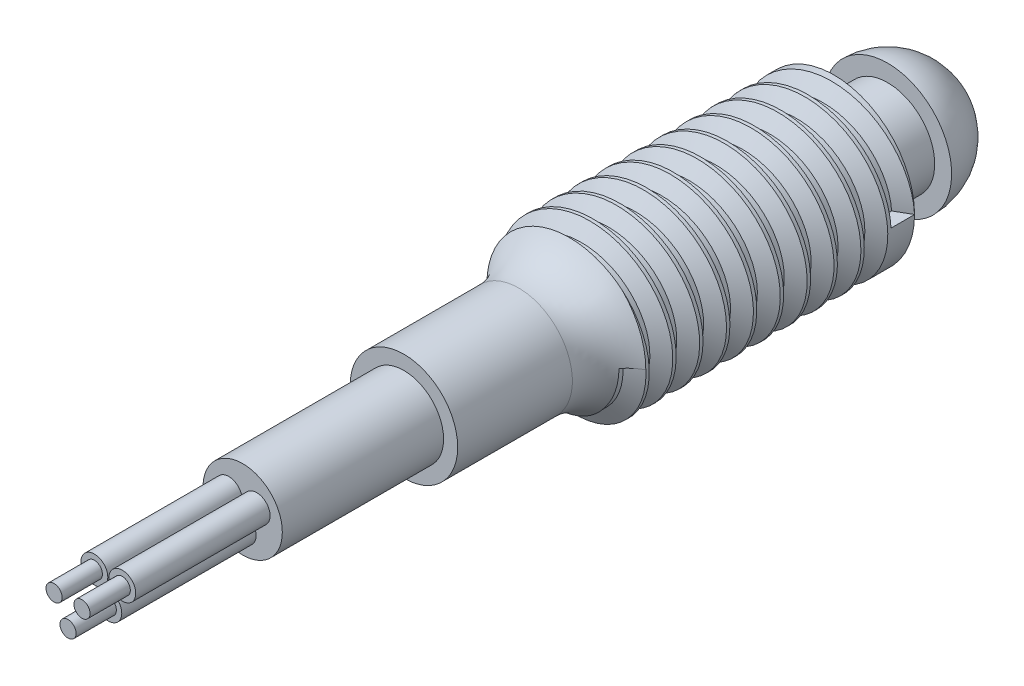
SolidWorks part; units mm, degrees
ref_plane "Front Plane" through (0, 0, 0) normal (0, 0, 1) x (1, 0, 0)
ref_plane "Top Plane" through (0, 0, 0) normal (0, 1, 0) x (1, 0, 0)
ref_plane "Right Plane" through (0, 0, 0) normal (1, 0, 0) x (0, 0, -1)
sketch "Sketch2" plane through (0, 0, 0) normal (0, 0, 1) x (1, 0, 0)
  line L0 (0, 3.833) -> (0, -4.6433) construction
  line L1 (0, 2.38) -> (0, -2.38)
  arc A0 (0, 2.38) -> (0, -2.38) centre (0, 0) ccw
  dimension "D1" = 4.76
revolve "Revolve2" add sketch "Sketch2" angle 180 about L0
sketch "Sketch3" plane through (0, 0, 0) normal (0, 0, 1) x (1, 0, 0)
  circle A0 centre (0, 0) radius 1.75
  dimension "D1" = 3.5
extrude "Boss-Extrude1" add sketch "Sketch3" along normal blind 2
sketch "Sketch4" plane through (0, 0, 2) normal (0, 0, 1) x (1, 0, 0)
  circle A0 centre (0, 0) radius 3
  dimension "D1" = 6
extrude "Boss-Extrude2" add sketch "Sketch4" along normal blind 10
sketch "Sketch5" plane through (0, 0, 12) normal (0, 0, 1) x (1, 0, 0)
  circle A0 centre (0, 0) radius 2
  dimension "D1" = 4
extrude "Boss-Extrude3" add sketch "Sketch5" along normal blind 6
fillet "Fillet1" radius 2 1 edges at (2, 0, 12)
sketch "Sketch6" plane through (0, 0, 18) normal (0, 0, 1) x (1, 0, 0)
  circle A0 centre (0, 0) radius 1.4745
extrude "Boss-Extrude4" add sketch "Sketch6" along normal blind 6
sketch "Sketch7" plane through (0, 0, 24) normal (0, 0, 1) x (1, 0, 0)
  line L0 (0, 0) -> (0, -0.6) construction
  line L1 (0, -0.6) -> (0.5196, 0.3) construction
  line L2 (0.5196, 0.3) -> (-0.5196, 0.3) construction
  line L3 (-0.5196, 0.3) -> (0, -0.6) construction
  circle A0 centre (0, 0) radius 0.3 construction
  circle A1 centre (-0.5196, 0.3) radius 0.5
  circle A2 centre (0.5196, 0.3) radius 0.5
  circle A3 centre (0, -0.6) radius 0.5
  dimension "D1" = 0.6
  dimension "D2" = 1
extrude "Boss-Extrude5" add sketch "Sketch7" along normal blind 5
sketch "Sketch8" plane through (0, 0, 29) normal (0, 0, 1) x (1, 0, 0)
  circle A0 centre (-0.5196, 0.3) radius 0.3
  circle A1 centre (0.5196, 0.3) radius 0.3
  circle A2 centre (0, -0.6) radius 0.3
  dimension "D1" = 0.6
extrude "Boss-Extrude6" add sketch "Sketch8" along normal blind 1.5
thread "Thread1" pitch 1 method cut profile "Thread Profile1" start angle 0, offset 0, length 10, pitch 1, diameter 6
ref_plane "Plane1" through (3, 0, 2) normal (0, -1, 0) x (1, 0, 0)
sketch "Thread Profile1" plane through (3, 0, 2) normal (0, -1, 0) x (1, 0, 0)
  line L0 (0, 0) -> (0, 1) construction
  line L11 (0, 0) -> (0, 0.875)
  line L12 (0, 0.875) -> (-0.5413, 0.5625)
  line L13 (-0.5413, 0.5625) -> (-0.5413, 0.3125)
  line L15 (-0.5413, 0.3125) -> (0, 0)
  line L17 (-0.5413, 0.4375) -> (0, 0.4375) construction
  point P2 (0, 0)
  dimension "Pitch" = 1
  dimension "Profile_Angle" = 60
  dimension "Profile_Land" = 0.25
  dimension "Profile_Height" = 0.5413
